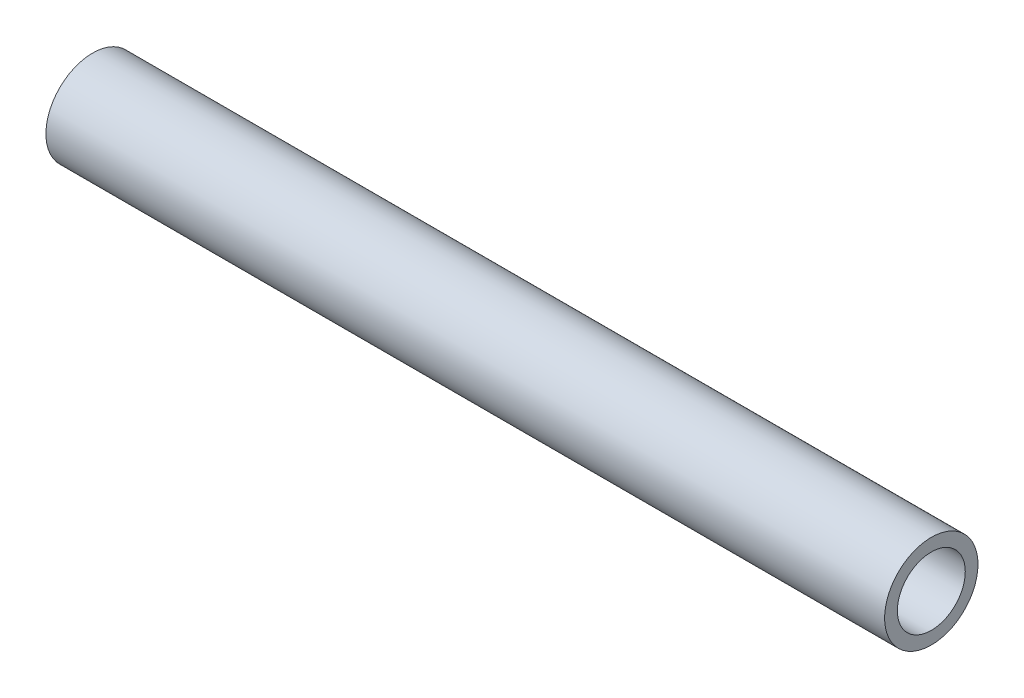
SolidWorks part; units mm, degrees
material "PVC Rígido"
ref_plane "Alzado" through (0, 0, 0) normal (0, 0, 1) x (1, 0, 0)
ref_plane "Planta" through (0, 0, 0) normal (0, 1, 0) x (1, 0, 0)
ref_plane "Vista lateral" through (0, 0, 0) normal (1, 0, 0) x (0, 0, -1)
sketch "Croquis1" plane through (0, 0, 0) normal (1, 0, 0) x (0, 0, -1)
  circle A0 centre (0, 0) radius 16.7
  circle A1 centre (0, 0) radius 12.15
  dimension "D1" = 33.4
  dimension "D2" = 24.3
extrude "Saliente-Extruir1" add sketch "Croquis1" along normal blind 300
